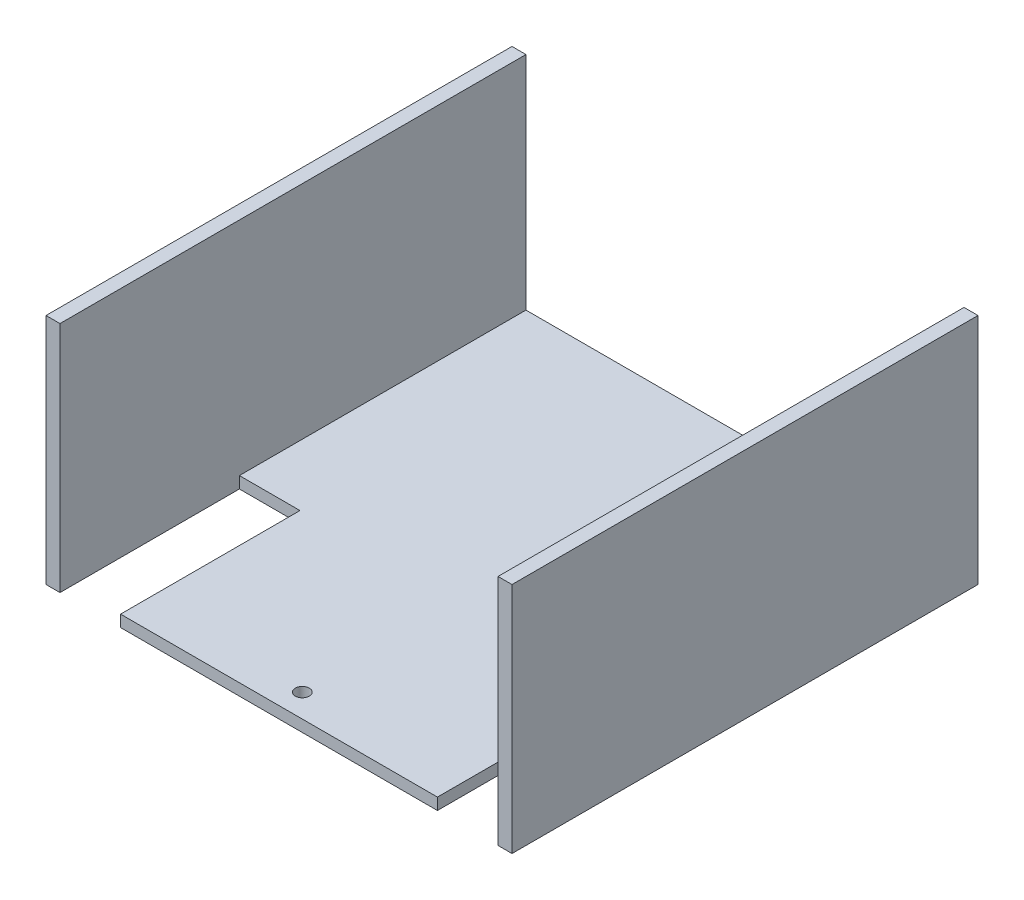
SolidWorks part; units mm, degrees
ref_plane "Alzado" through (0, 0, 0) normal (0, 0, 1) x (1, 0, 0)
ref_plane "Planta" through (0, 0, 0) normal (0, 1, 0) x (1, 0, 0)
ref_plane "Vista lateral" through (0, 0, 0) normal (1, 0, 0) x (0, 0, -1)
sketch "Croquis1" plane through (0, 0, 0) normal (0, 0, 1) x (1, 0, 0)
  line L0 (50, 0) -> (-50, 0)
  line L1 (-50, 0) -> (-50, 50)
  line L2 (-50, 50) -> (-47, 50)
  line L3 (-47, 50) -> (-47, 2.5)
  line L4 (-47, 2.5) -> (47, 2.5)
  line L5 (0, 2.5) -> (0, 0)
  line L6 (0, 0) -> (0, 13.9963) construction
  line L7 (47, 50) -> (47, 2.5)
  line L8 (50, 50) -> (47, 50)
  line L9 (50, 0) -> (50, 50)
  dimension "D1" = 50
  dimension "D2" = 50
  dimension "D3" = 3
  dimension "D4" = 2.5
extrude "Saliente-Extruir1" add sketch "Croquis1" against normal blind 100 contours L4 L7 L8 L9 L0 L1 L2 L3
sketch "Croquis2" plane through (0, 2.5, 0) normal (0, 1, 0) x (1, 0, 0)
  line L0 (0, 0) -> (0, 100) construction
  line L1 (-47, 0) -> (-34, 0)
  line L2 (-47, 0) -> (-47, 38.5)
  line L3 (-47, 38.5) -> (-34, 38.5)
  line L4 (-34, 0) -> (-34, 38.5)
  line L5 (-47, 100) -> (47, 100) construction
  line L6 (47, 38.5) -> (34, 38.5)
  line L7 (34, 0) -> (34, 38.5)
  line L8 (47, 0) -> (34, 0)
  line L9 (47, 0) -> (47, 38.5)
  dimension "D1" = 13
  dimension "D2" = 38.5
extrude "Cortar-Extruir2" cut sketch "Croquis2" against normal blind 10
ref_plane "Plano1" through (0, 2.5, 0) normal (0, 1, 0) x (1, 0, 0)
sketch "Croquis3" plane through (0, 2.5, 0) normal (0, 1, 0) x (1, 0, 0)
  line L0 (0, 0) -> (0, 100) construction
  line L1 (-47, 100) -> (47, 100) construction
  line L2 (-34, 0) -> (34, 0) construction
  circle A1 centre (0, 5) radius 1.5
  dimension "D1" = 3
  dimension "D2" = 5
extrude "Cortar-Extruir3" cut sketch "Croquis3" against normal blind 5
